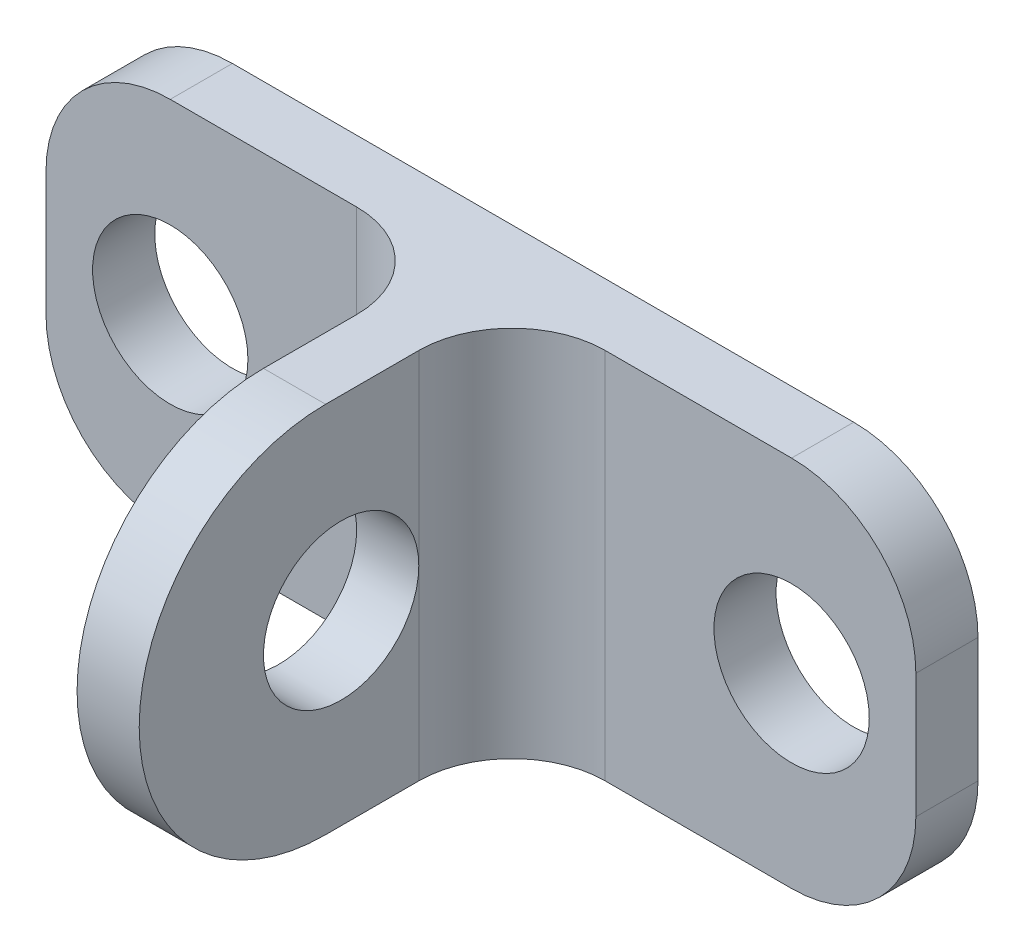
SolidWorks part; units mm, degrees
ref_plane "Alzado" through (0, 0, 0) normal (0, 0, 1) x (1, 0, 0)
ref_plane "Planta" through (0, 0, 0) normal (0, 1, 0) x (1, 0, 0)
ref_plane "Vista lateral" through (0, 0, 0) normal (1, 0, 0) x (0, 0, -1)
sketch "Croquis1" plane through (0, 0, 0) normal (0, 0, 1) x (1, 0, 0)
  line L0 (-85, -3) -> (73.395, -3) construction
  line L1 (-5, -3) -> (5, -3)
  line L2 (-7, -1) -> (-7, 1)
  line L3 (-5, 3) -> (5, 3)
  line L4 (7, -1) -> (7, 1)
  line L5 (66.355, 3) -> (-85, 3) construction
  line L6 (0, 3) -> (0, -3) construction
  line L7 (-5, 0) -> (5, 0) construction
  line L8 (5, 0) -> (0, 0) construction
  circle A2 centre (-5, 0) radius 1.25
  circle A3 centre (5, 0) radius 1.25
  arc A4 (5, 3) -> (7, 1) centre (5, 1) cw
  arc A5 (7, -1) -> (5, -3) centre (5, -1) cw
  arc A6 (-5, -3) -> (-7, -1) centre (-5, -1) cw
  arc A7 (-7, 1) -> (-5, 3) centre (-5, 1) cw
  point P21 (7, 3)
  point P24 (7, -3)
  point P27 (-7, -3)
  dimension "D2" = 2
  dimension "D4" = 2.5
  dimension "D1" = 14
  dimension "D3" = 10
extrude "Saliente-Extruir1" add sketch "Croquis1" along normal blind 1 contours A7 L2 A6 L1 A5 A3 A4 L3 A2 region at (0, 0, 0)
sketch "Croquis2" plane through (0, 0, 1) normal (0, 0, 1) x (1, 0, 0)
  line L0 (0, 3) -> (0, -3) construction
  line L3 (0, -3) -> (0, 0) construction
  line L4 (-0.5, 3) -> (-0.5, -3)
  line L5 (-0.5, 3) -> (0.5, 3)
  line L6 (-0.5, -3) -> (0.5, -3)
  line L7 (0.5, 3) -> (0.5, -3)
  line L8 (-0.5, 3) -> (0.5, -3) construction
  line L9 (-0.5, -3) -> (0.5, 3) construction
  line L10 (-5, -3) -> (5, -3) construction
  line L11 (-5, 3) -> (5, 3) construction
  dimension "D1" = 1
extrude "Saliente-Extruir2" add sketch "Croquis2" along normal blind 6
fillet "Redondeo1" 2 edges at (0, 3, 7) (0, -3, 7) type full round first side face at (-0.5625, 3, 3) second side face at (-0.5625, -3, 3) middle face at (0, 0, 7)
sketch "Croquis3" plane through (-0.5, 0, 0) normal (-1, 0, 0) x (0, 0, 1)
  line L0 (2.5, 0) -> (7, 0) construction
  arc A0 (4, -3) -> (4, 3) centre (4, 0) ccw construction
  circle A1 centre (3.75, 0) radius 1.25
  dimension "D1" = 2.5
  dimension "D2" = 4.5
extrude "Cortar-Extruir1" cut sketch "Croquis3" against normal up to next
fillet "Redondeo2" radius 1.5 2 edges
